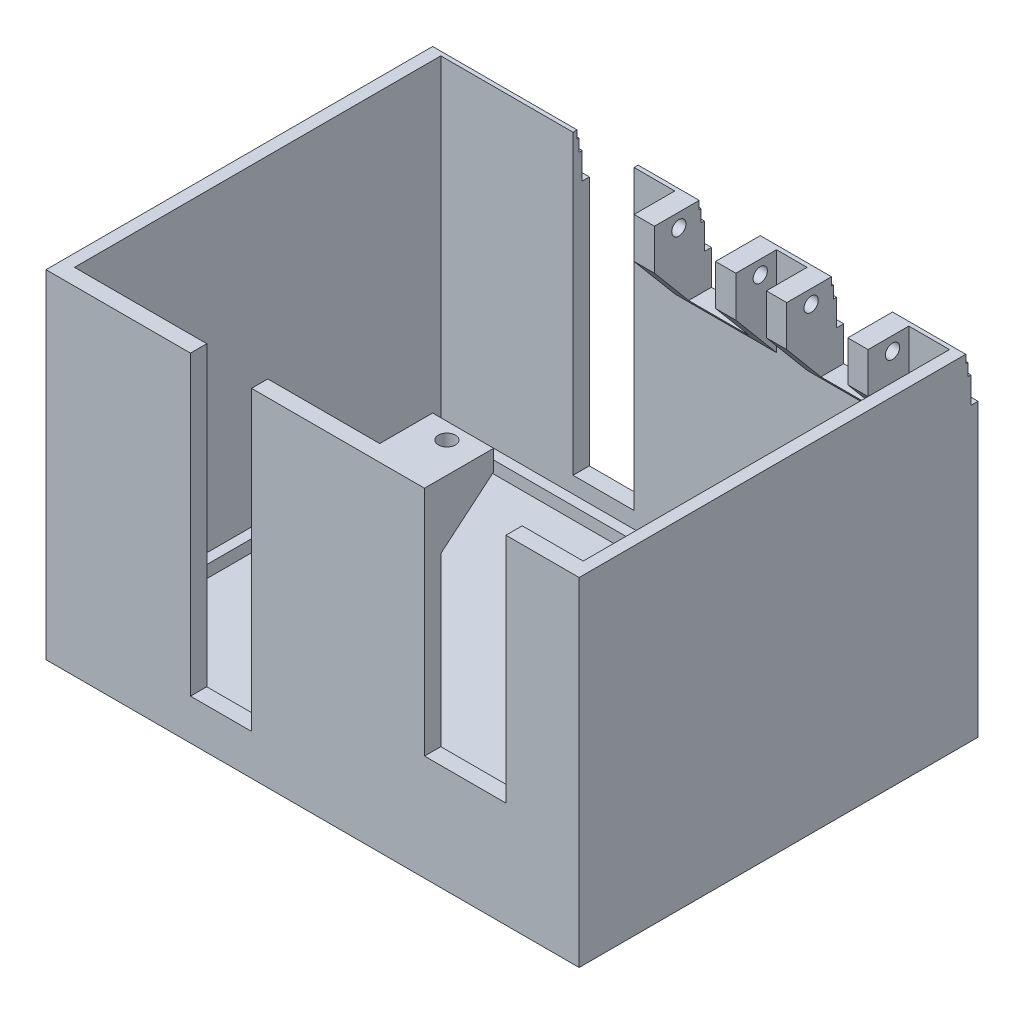
SolidWorks part; units mm, degrees
ref_plane "Front Plane" through (0, 0, 0) normal (0, 0, 1) x (1, 0, 0)
ref_plane "Top Plane" through (0, 0, 0) normal (0, 1, 0) x (1, 0, 0)
ref_plane "Right Plane" through (0, 0, 0) normal (1, 0, 0) x (0, 0, -1)
sketch "Sketch1" plane through (0, 0, 0) normal (0, 1, 0) x (1, 0, 0)
  line L1 (62.5, -45) -> (-62.5, -45)
  line L2 (62.5, -45) -> (62.5, 45)
  line L3 (62.5, 45) -> (-62.5, 45)
  line L4 (-62.5, -45) -> (-62.5, 45)
  line L5 (62.5, -45) -> (-62.5, 45) construction
  line L6 (62.5, 45) -> (-62.5, -45) construction
  line L7 (65.5, -49) -> (-65.5, -49)
  line L8 (65.5, -49) -> (65.5, 49)
  line L9 (65.5, 49) -> (-65.5, 49)
  line L10 (-65.5, -49) -> (-65.5, 49)
  line L11 (65.5, -49) -> (-65.5, 49) construction
  line L12 (65.5, 49) -> (-65.5, -49) construction
  point P0 (0, 0)
  point P5 (0, 0)
  dimension "D4" = 4
  dimension "D1" = 125
  dimension "D2" = 90
  dimension "D3" = 3
extrude "Boss-Extrude1" add sketch "Sketch1" along normal blind 80
sketch "Sketch2" plane through (0, 0, 0) normal (0, -1, 0) x (1, 0, 0)
  line L1 (65.5, -49) -> (-65.5, -49)
  line L2 (65.5, -49) -> (65.5, 49)
  line L3 (65.5, 49) -> (-65.5, 49)
  line L4 (-65.5, -49) -> (-65.5, 49)
extrude "Boss-Extrude2" add sketch "Sketch2" along normal blind 3
sketch "Sketch4" plane through (0, 0, 0) normal (0, 1, 0) x (1, 0, 0)
  line L1 (-62.5, 45) -> (62.5, 45)
  line L2 (-62.5, 45) -> (-62.5, -45)
  line L3 (-62.5, -45) -> (62.5, -45)
  line L4 (62.5, 45) -> (62.5, -45)
  line L5 (59.5, -42) -> (-60, -42)
  line L6 (59.5, -42) -> (59.5, 42.5)
  line L7 (59.5, 42.5) -> (-60, 42.5)
  line L8 (-60, -42) -> (-60, 42.5)
  dimension "D1" = 2.5
  dimension "D2" = 2.5
  dimension "D3" = 3
  dimension "D4" = 3
extrude "Boss-Extrude3" add sketch "Sketch4" along normal blind 3
sketch "Sketch5" plane through (0, 0, -49) normal (0, 0, -1) x (-1, 0, 0)
  line L0 (-65.5, 80) -> (65.5, 80) construction
  line L1 (15, 80) -> (30, 80)
  line L2 (15, 80) -> (15, 7)
  line L3 (15, 7) -> (30, 7)
  line L4 (30, 80) -> (30, 7)
  line L5 (15, 80) -> (30, 7) construction
  line L6 (15, 7) -> (30, 80) construction
  line L7 (62.5, 74.3372) -> (62.5, 12.8298) construction
  line L8 (65.5, 80) -> (65.5, -3) construction
  line L9 (65.5, -3) -> (-65.5, -3) construction
  point P0 (22.5, 43.5)
  dimension "D1" = 3
  dimension "D2" = 40
  dimension "D3" = 15
  dimension "D4" = 10
extrude "Cut-Extrude1" cut sketch "Sketch5" against normal through all
sketch "Sketch6" plane through (0, 0, 45) normal (0, 0, -1) x (-1, 0, 0)
  line L0 (15, 80) -> (-62.5, 80) construction
  line L1 (-27.5, 23) -> (-47.5, 23)
  line L2 (-27.5, 23) -> (-27.5, 80)
  line L3 (-27.5, 80) -> (-47.5, 80)
  line L4 (-47.5, 23) -> (-47.5, 80)
  line L5 (-27.5, 23) -> (-47.5, 80) construction
  line L6 (-27.5, 80) -> (-47.5, 23) construction
  line L7 (62.5, 3) -> (-62.5, 3) construction
  line L8 (-62.5, 80) -> (-62.5, 3) construction
  point P0 (-37.5, 51.5)
  dimension "D1" = 20
  dimension "D2" = 20
  dimension "D3" = 25
extrude "Cut-Extrude2" cut sketch "Sketch6" against normal up to next
sketch "Sketch7" plane through (0, 0, -45) normal (0, 0, 1) x (1, 0, 0)
  line L0 (62.5, 80) -> (-15, 80) construction
  line L1 (32.5, 80) -> (47.5, 80)
  line L2 (32.5, 80) -> (32.5, 60)
  line L3 (32.5, 60) -> (47.5, 60)
  line L4 (47.5, 80) -> (47.5, 60)
  line L5 (65.5, 80) -> (65.5, -3) construction
  line L6 (0, 80) -> (15, 80)
  line L7 (0, 80) -> (0, 60)
  line L8 (0, 60) -> (15, 60)
  line L9 (15, 80) -> (15, 60)
  dimension "D1" = 20
  dimension "D2" = 18
  dimension "D3" = 15
  dimension "D4" = 15
  dimension "D5" = 17.5
extrude "Cut-Extrude3" cut sketch "Sketch7" against normal up to next
sketch "Sketch8" plane through (0, 0, -45) normal (0, 0, 1) x (1, 0, 0)
  line L1 (0, 80) -> (-5, 80)
  line L2 (0, 80) -> (0, 70)
  line L3 (0, 70) -> (-5, 70)
  line L4 (-5, 80) -> (-5, 70)
  line L5 (15, 80) -> (20, 80)
  line L6 (15, 80) -> (15, 70)
  line L7 (15, 70) -> (20, 70)
  line L8 (20, 80) -> (20, 70)
  line L9 (32.5, 80) -> (27.5, 80)
  line L10 (32.5, 80) -> (32.5, 70)
  line L11 (32.5, 70) -> (27.5, 70)
  line L12 (27.5, 80) -> (27.5, 70)
  line L13 (47.5, 80) -> (52.5, 80)
  line L14 (47.5, 80) -> (47.5, 70)
  line L15 (47.5, 70) -> (52.5, 70)
  line L16 (52.5, 80) -> (52.5, 70)
  dimension "D1" = 5
  dimension "D2" = 5
  dimension "D3" = 10
  dimension "D4" = 5
  dimension "D5" = 5
extrude "Boss-Extrude4" add sketch "Sketch8" along normal blind 10
sketch "Skizze2" plane through (-5, 0, 0) normal (-1, 0, 0) x (0, 0, 1)
  line L0 (-35, 70) -> (-45, 70)
  line L1 (-45, 70) -> (-45, 58.0825)
  line L2 (-45, 58.0825) -> (-35, 70)
  dimension "D1" = 40
extrude "3D Printer Support" add sketch "Skizze2" against normal up to vertex (57.5 mm away) up to point (52.5, 70, -35)
sketch "Skizze3" plane through (0, 0, -45) normal (0, 0, -1) x (-1, 0, 0)
  line L1 (-32.5, 70) -> (-47.5, 70)
  line L2 (-32.5, 70) -> (-32.5, 60)
  line L3 (-32.5, 60) -> (-47.5, 60)
  line L4 (-47.5, 70) -> (-47.5, 60)
  line L5 (-15, 60) -> (0, 60)
  line L6 (-15, 60) -> (-15, 70)
  line L7 (-15, 70) -> (0, 70)
  line L8 (0, 60) -> (0, 70)
extrude "Schnitt-Linear austragen1" cut sketch "Skizze3" against normal blind 20
sketch "Skizze4" plane through (0, 70, 0) normal (0, 1, 0) x (1, 0, 0)
  line L1 (27.5, 45) -> (20, 45)
  line L2 (27.5, 45) -> (27.5, 35)
  line L3 (27.5, 35) -> (20, 35)
  line L4 (20, 45) -> (20, 35)
extrude "Schnitt-Linear austragen2" cut sketch "Skizze4" against normal blind 20
sketch "Skizze5" plane through (-5, 0, 0) normal (-1, 0, 0) x (0, 0, 1)
  line L1 (-35, 80) -> (-45, 80) construction
  line L2 (-49, 60) -> (-49, 80) construction
  circle A0 centre (-41, 76.6459) radius 1.75
  point P5 (-40, 80)
  dimension "D3" = 3.5
  dimension "D1" = 8
  dimension "D2" = 3.5
extrude "Schnitt-Linear austragen3" cut sketch "Skizze5" against normal up to surface (57.5 mm away) up to face at (52.5, 72.0206, -40)
ref_plane "Ebene1" through (27.5, 0, 0) normal (1, 0, 0) x (0, 0, -1)
sketch "Skizze9" plane through (27.5, 0, 0) normal (1, 0, 0) x (0, 0, -1)
  line L0 (-45, 80) -> (-32, 80)
  line L1 (-32, 80) -> (-32, 75)
  line L2 (-32, 75) -> (-45, 64.0917)
  line L3 (-45, 64.0917) -> (-45, 80)
  line L4 (-45, 23) -> (-45, 80) construction
  line L5 (-49, 80) -> (-45, 80) construction
  line L6 (-39, 80) -> (-39, 58.0539) construction
  line L7 (-42.2981, 66) -> (6.0171, 66) construction
  dimension "D1" = 13
  dimension "D2" = 50
  dimension "D3" = 5
  dimension "D4" = 14
  dimension "D5" = 6
extrude "Aufsatz-Linear austragen2" add sketch "Skizze9" against normal blind 15
sketch "Skizze10" plane through (0, 80, 0) normal (0, 1, 0) x (1, 0, 0)
  line L0 (27.5, -49) -> (27.5, -32) construction
  line L1 (12.5, -45) -> (27.5, -45) construction
  line L2 (65.5, -49) -> (65.5, 49) construction
  circle A0 centre (20, -36) radius 2.1
  dimension "D1" = 4.2
  dimension "D2" = 9
  dimension "D3" = 7.5
  dimension "D4" = 45.5
extrude "Schnitt-Linear austragen4" cut sketch "Skizze10" against normal up to vertex (15.9083 mm away) up to point (12.5, 64.0917, 45)
sketch "Sketch9" plane through (-65.5, 0, 0) normal (-1, 0, 0) x (0, 0, 1)
  line L0 (-46, 78) -> (-46.5, 78)
  line L1 (-49, 80) -> (-46, 80)
  line L2 (-49, 68.5) -> (-49, 80)
  line L3 (-47.25, 75) -> (-47.25, 68.5)
  line L4 (-46, 80) -> (-46, 78)
  line L5 (-47.25, 68.5) -> (-49, 68.5)
  line L6 (-49, 80) -> (-49, -3) construction
  line L7 (-46.5, 78) -> (-46.5, 75)
  line L8 (-46.5, 75) -> (-47.25, 75)
  dimension "D1" = 1.75
  dimension "D2" = 2
  dimension "D3" = 6.5
  dimension "D4" = 3
  dimension "D5" = 0.5
  dimension "D6" = 3
extrude "Cut-Extrude4" cut sketch "Sketch9" against normal up to surface (131 mm away) up to face at (65.5, 38.5, 0)
